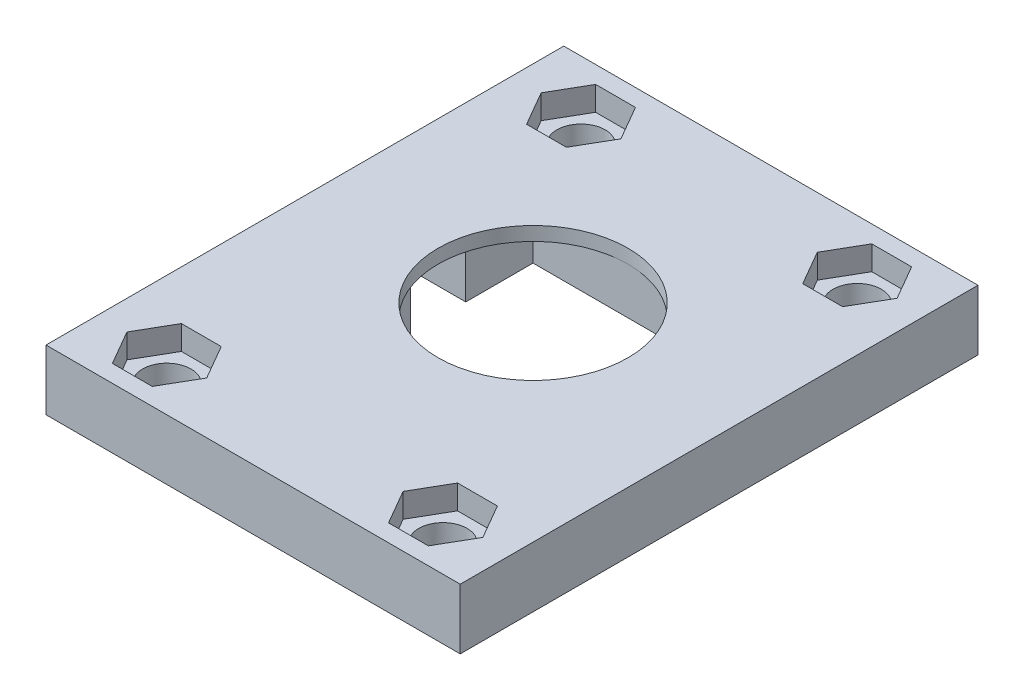
SolidWorks part; units mm, degrees
material "ABS"
ref_plane "Front Plane" through (0, 0, 0) normal (0, 0, 1) x (1, 0, 0)
ref_plane "Top Plane" through (0, 0, 0) normal (0, 1, 0) x (1, 0, 0)
ref_plane "Right Plane" through (0, 0, 0) normal (1, 0, 0) x (0, 0, -1)
sketch "Sketch1" plane through (0, 0, 0) normal (0, 1, 0) x (1, 0, 0)
  line L1 (15.24, -19.05) -> (-15.24, -19.05)
  line L2 (15.24, -19.05) -> (15.24, 19.05)
  line L3 (15.24, 19.05) -> (-15.24, 19.05)
  line L4 (-15.24, -19.05) -> (-15.24, 19.05)
  line L5 (15.24, -19.05) -> (-15.24, 19.05) construction
  line L6 (15.24, 19.05) -> (-15.24, -19.05) construction
  line L10 (-15.24, 0) -> (49984.76, 0) construction
  line L11 (0, 18.415) -> (0, -49981.585) construction
  circle A0 centre (-10.16, 15.24) radius 1.778
  circle A1 centre (10.16, 15.24) radius 1.778
  circle A2 centre (-10.16, -15.24) radius 1.778
  circle A3 centre (10.16, -15.24) radius 1.778
  point P0 (0, 0)
  point P8 (-15.24, 0)
  point P9 (15.24, 0)
  point P12 (0, 19.05)
  point P13 (0, -19.05)
  dimension "D3" = 3.556
  dimension "D4" = 30.48
  dimension "D5" = 20.32
  dimension "D1" = 38.1
  dimension "D2" = 30.48
extrude "Boss-Extrude1" add sketch "Sketch1" along normal blind 4.445
sketch "Sketch2" plane through (0, 0, 0) normal (0, -1, 0) x (1, 0, 0)
  line L0 (0, 15.24) -> (0, -49984.76) construction
  line L1 (-10.16, 15.24) -> (10.16, 15.24) construction
  line L2 (-10.16, 15.24) -> (-10.16, -15.24) construction
  line L3 (-10.16, -15.24) -> (10.16, -15.24) construction
  line L4 (10.16, 15.24) -> (10.16, -15.24) construction
  circle A0 centre (-10.16, -15.24) radius 1.778 construction
  circle A1 centre (10.16, -15.24) radius 1.778 construction
  circle A2 centre (10.16, 15.24) radius 1.778 construction
  circle A3 centre (-10.16, 15.24) radius 1.778 construction
  circle A4 centre (-10.16, -15.24) radius 1.778
  circle A5 centre (10.16, -15.24) radius 1.778
  circle A6 centre (10.16, 15.24) radius 1.778
  circle A7 centre (-10.16, 15.24) radius 1.778
  circle A8 centre (0, -1.5494) radius 6.985
  point P15 (0, -15.24)
  point P19 (0, 15.24)
  dimension "D1" = 13.97
  dimension "D2" = 13.6906
extrude "Cut-Extrude1" cut sketch "Sketch2" against normal through all
sketch "Sketch3" plane through (0, 0, 0) normal (0, -1, 0) x (1, 0, 0)
  line L0 (-6.985, -8.5344) -> (6.985, -8.5344)
  line L1 (-6.985, -8.5344) -> (-6.985, 5.4356)
  line L2 (6.985, -8.5344) -> (6.985, 5.4356)
  line L3 (-6.985, 5.4356) -> (6.985, 5.4356)
  line L4 (-6.985, -8.5344) -> (6.985, 5.4356) construction
  line L5 (6.985, -8.5344) -> (-6.985, 5.4356) construction
  line L6 (0, -8.5344) -> (0, 49991.4656) construction
  line L8 (-11.049, 0.4826) -> (-6.985, 0.4826)
  line L9 (-11.049, 0.4826) -> (-11.049, -3.5814)
  line L10 (-11.049, -3.5814) -> (-6.985, -3.5814)
  line L11 (-6.985, 0.4826) -> (-6.985, -3.5814)
  line L15 (11.049, -3.5814) -> (6.985, -3.5814)
  line L16 (6.985, 0.4826) -> (6.985, -3.5814)
  line L17 (11.049, 0.4826) -> (6.985, 0.4826)
  line L18 (11.049, 0.4826) -> (11.049, -3.5814)
  line L19 (-6.985, -1.5494) -> (49993.015, -1.5494) construction
  circle A0 centre (0, -1.5494) radius 6.985 construction
  point P3 (0, 5.4356)
  point P4 (6.985, -1.5494)
  point P13 (0, -8.5344)
  point P21 (-6.985, -1.5494)
  circle M13 centre (0, -1.5494) radius 6.985
  dimension "D1" = 4.064
  dimension "D2" = 2.032
  dimension "D3" = 2.032
extrude "Cut-Extrude2" cut sketch "Sketch3" against normal blind 3.429 contours L1 L0 M13 | L3 L1 M13 | L3 L2 M13 | L2 | L9 L10 L1 L8 | L0 L2 M13 region at (-5.4248, 0, -6.9742) region at (5.4248, 0, -6.9742) region at (-9.017, 0, -1.5494) region at (-5.4248, 0, 3.8754) region at (9.017, 0, -1.5494) region at (5.4248, 0, 3.8754)
sketch "Sketch4" plane through (0, 4.445, 0) normal (0, 1, 0) x (1, 0, 0)
  line L0 (0, -19.05) -> (0, 49980.95) construction
  line L1 (-7.2271, 15.24) -> (-8.6935, 17.78)
  line L2 (-8.6935, 17.78) -> (-11.6265, 17.78)
  line L3 (-11.6265, 17.78) -> (-13.0929, 15.24)
  line L4 (-15.24, 19.05) -> (-15.24, -19.05)
  line L5 (-15.24, -19.05) -> (15.24, -19.05)
  line L6 (15.24, -19.05) -> (15.24, 19.05)
  line L7 (15.24, 19.05) -> (-15.24, 19.05)
  line L8 (-15.24, 19.05) -> (-15.24, -19.05) construction
  line L9 (-15.24, -19.05) -> (15.24, -19.05) construction
  line L10 (15.24, -19.05) -> (15.24, 19.05) construction
  line L11 (15.24, 19.05) -> (-15.24, 19.05) construction
  line L12 (-13.0929, 15.24) -> (-11.6265, 12.7)
  line L13 (-11.6265, 12.7) -> (-8.6935, 12.7)
  line L14 (-8.6935, 12.7) -> (-7.2271, 15.24)
  line L15 (-15.24, 0) -> (49984.76, 0) construction
  line L16 (8.6935, 12.7) -> (7.2271, 15.24)
  line L17 (11.6265, 12.7) -> (8.6935, 12.7)
  line L18 (13.0929, 15.24) -> (11.6265, 12.7)
  line L19 (11.6265, 17.78) -> (13.0929, 15.24)
  line L20 (8.6935, 17.78) -> (11.6265, 17.78)
  line L21 (7.2271, 15.24) -> (8.6935, 17.78)
  line L22 (11.6265, -12.7) -> (8.6935, -12.7)
  line L23 (13.0929, -15.24) -> (11.6265, -12.7)
  line L24 (11.6265, -17.78) -> (13.0929, -15.24)
  line L25 (8.6935, -17.78) -> (11.6265, -17.78)
  line L26 (7.2271, -15.24) -> (8.6935, -17.78)
  line L27 (8.6935, -12.7) -> (7.2271, -15.24)
  line L28 (-8.6935, -12.7) -> (-7.2271, -15.24)
  line L29 (-11.6265, -12.7) -> (-8.6935, -12.7)
  line L30 (-13.0929, -15.24) -> (-11.6265, -12.7)
  line L31 (-11.6265, -17.78) -> (-13.0929, -15.24)
  line L32 (-8.6935, -17.78) -> (-11.6265, -17.78)
  line L33 (-7.2271, -15.24) -> (-8.6935, -17.78)
  circle A0 centre (-10.16, 15.24) radius 2.54 construction
  point P15 (0, -19.05)
  point P16 (0, 19.05)
  point P19 (-15.24, 0)
  point P20 (15.24, 0)
  dimension "D2" = 5.08
  dimension "D1" = 0
extrude "Cut-Extrude3" cut sketch "Sketch4" against normal blind 1.778
